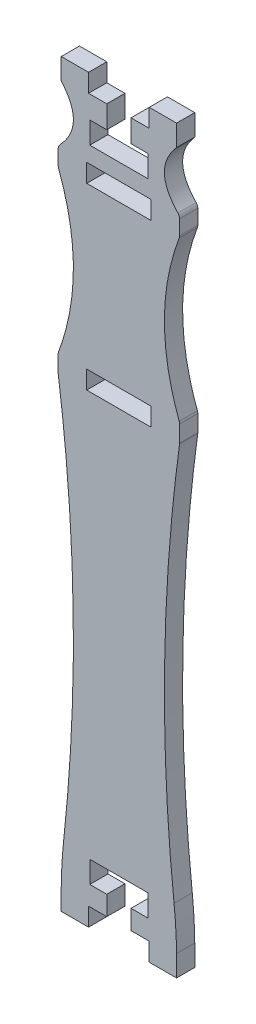
SolidWorks part; units mm, degrees
ref_plane "Alzado" through (0, 0, 0) normal (0, 0, 1) x (1, 0, 0)
ref_plane "Planta" through (0, 0, 0) normal (0, 1, 0) x (1, 0, 0)
ref_plane "Vista lateral" through (0, 0, 0) normal (1, 0, 0) x (0, 0, -1)
sketch "Croquis1" plane through (0, 0, 0) normal (0, 0, 1) x (1, 0, 0)
  line L1 (-10, 70) -> (-10, 67)
  line L2 (-7, 67) -> (-10, 67)
  line L4 (-15, 70) -> (-15, 67.4057)
  line L6 (-7, -45.5) -> (-7, -49)
  line L7 (-0.5, -42.5) -> (-9.5, -42.5)
  line L9 (-10, 70) -> (-15, 70)
  line L10 (-9.5, 60) -> (-0.5, 60)
  line L11 (-10, -52) -> (-10, -49)
  line L12 (-10, -52) -> (-15, -52)
  line L13 (-0.5, -42.5) -> (-0.5, -45.5)
  line L14 (-0.5, -45.5) -> (-3, -45.5)
  line L15 (-15, -52) -> (-15, -51.7014)
  line L16 (0, -49) -> (0, -52)
  line L17 (-0.5, 60) -> (-0.5, 63)
  line L18 (-3, -45.5) -> (-3, -49)
  line L19 (-0.5, 63) -> (-3, 63)
  line L20 (-10, 27.5) -> (-10, 24.5)
  line L21 (-3, 63) -> (-3, 67)
  line L22 (-10, 24.5) -> (0, 24.5)
  line L23 (0, 24.5) -> (0, 27.5)
  line L24 (-7, 63) -> (-7, 67)
  line L25 (-15, 27.3187) -> (-15, 24.5677)
  line L26 (-9.5, -45.5) -> (-7, -45.5)
  line L27 (-9.5, -42.5) -> (-9.5, -45.5)
  line L28 (-7, -49) -> (-10, -49)
  line L29 (-9.5, 63) -> (-7, 63)
  line L30 (-9.5, 60) -> (-9.5, 63)
  line L31 (-10, 54) -> (-10, 57)
  line L32 (-10, 54) -> (0, 54)
  line L33 (-10, 57) -> (0, 57)
  line L34 (0, 57) -> (0, 54)
  line L35 (-3, 67) -> (0, 67)
  line L36 (0, -52) -> (5, -52)
  line L37 (0, 67) -> (0, 70)
  line L38 (5, 70) -> (0, 70)
  line L39 (5, -52) -> (5, -51.7014)
  line L40 (0, 27.5) -> (-10, 27.5)
  line L42 (-15, 56.5943) -> (-15, 54.1813)
  line L43 (0, -49) -> (-3, -49)
  line L46 (-15, -49.0677) -> (-15, -51.7014)
  line L51 (5, -51.7014) -> (5, -49.0677)
  line L53 (5, 24.5677) -> (5, 27.3187)
  line L55 (5, 54.1813) -> (5, 56.5943)
  line L57 (5, 67.4057) -> (5, 70)
  arc A4 (-14.9909, -48.9331) -> (-15, -49.0677) centre (-14, -49.0677) ccw
  arc A5 (5, -49.0677) -> (4.9909, -48.9331) centre (4, -49.0677) ccw
  arc A6 (-15, 24.5677) -> (-14.9909, 24.4331) centre (-14, 24.5677) ccw
  arc A7 (4.9909, 24.4331) -> (5, 24.5677) centre (4, 24.5677) ccw
  arc A8 (-14.9371, 27.6678) -> (-15, 27.3187) centre (-14, 27.3187) ccw
  arc A9 (5, 27.3187) -> (4.9371, 27.6678) centre (4, 27.3187) ccw
  arc A10 (-14.7272, 57.2807) -> (-15, 56.5943) centre (-14, 56.5943) ccw
  arc A11 (-15, 54.1813) -> (-14.9371, 53.8322) centre (-14, 54.1813) ccw
  arc A12 (4.9371, 53.8322) -> (5, 54.1813) centre (4, 54.1813) ccw
  arc A13 (5, 56.5943) -> (4.7272, 57.2807) centre (4, 56.5943) ccw
  arc A14 (4.7272, 66.7193) -> (5, 67.4057) centre (4, 67.4057) ccw
  arc A15 (-15, 67.4057) -> (-14.7272, 66.7193) centre (-14, 67.4057) ccw
  spline S0 degree 3 poles (4.7272, 66.7193) (3.2424, 65.1462) (1.7576, 62) (3.2424, 58.8538) (4.7272, 57.2807) knots 0.028065 0.028065 0.028065 0.028065 0.5 0.971935 0.971935 0.971935 0.971935
  spline S1 degree 3 poles (-14.7272, 57.2807) (-13.2424, 58.8538) (-11.7576, 62) (-13.2424, 65.1462) (-14.7272, 66.7193) knots 0.028065 0.028065 0.028065 0.028065 0.5 0.971935 0.971935 0.971935 0.971935
  spline S2 degree 3 poles (-14.9371, 53.8322) (-13.3124, 49.4715) (-11.6876, 40.75) (-13.3124, 32.0285) (-14.9371, 27.6678) knots 0.006333 0.006333 0.006333 0.006333 0.5 0.993667 0.993667 0.993667 0.993667
  spline S3 degree 3 poles (4.9371, 53.8322) (3.3124, 49.4715) (1.6876, 40.75) (3.3124, 32.0285) (4.9371, 27.6678) knots 0.006333 0.006333 0.006333 0.006333 0.5 0.993667 0.993667 0.993667 0.993667
  spline S4 degree 3 poles (-14.9909, -48.9331) (-13.3303, -36.7054) (-11.6697, -12.25) (-13.3303, 12.2054) (-14.9909, 24.4331) knots 0.00091 0.00091 0.00091 0.00091 0.5 0.99909 0.99909 0.99909 0.99909
  spline S7 degree 3 poles (4.9909, -48.9331) (3.3303, -36.7054) (1.6697, -12.25) (3.3303, 12.2054) (4.9909, 24.4331) knots 0.00091 0.00091 0.00091 0.00091 0.5 0.99909 0.99909 0.99909 0.99909
extrude "Saliente-Extruir1" add sketch "Croquis1" along normal blind 3 contours L38 | L38 L37 L1 L9 L28 L6 L26 L27 L7 L13 L14 L18 L43 A6 A8 region at (-5, 8.2674, 0)
sketch "Croquis2" plane through (0, 0, 3) normal (0, 0, 1) x (1, 0, 0)
  line L0 (-3, 63) -> (-3, 67) construction
  line L1 (-9.5, 60) -> (-0.5, 60)
  line L3 (-9.5, 59.7) -> (-0.5, 59.7)
  line L5 (-0.5, 63) -> (-3, 63)
  line L7 (-0.5, 63.3) -> (-3, 63.3)
  line L8 (-3, 63) -> (-3, 63.3)
  line L9 (-3, -45.5) -> (-3, -49) construction
  line L10 (-7, 63) -> (-9.5, 63)
  line L11 (-7, 63) -> (-7, 63.3)
  line L12 (-7, 63.3) -> (-9.5, 63.3)
  line L15 (-9.5, 63) -> (-9.5, 60)
  line L17 (-9.8, 63) -> (-9.8, 60)
  line L19 (-0.5, 63) -> (-0.5, 60)
  line L21 (-0.2, 63) -> (-0.2, 60)
  line L22 (-0.5, -42.5) -> (-9.5, -42.5)
  line L23 (-0.5, -42.5) -> (-0.5, -42.2)
  line L24 (-0.5, -42.2) -> (-9.5, -42.2)
  line L27 (-0.5, -45.5) -> (-0.5, -42.5)
  line L28 (-0.5, -42.5) -> (-0.2, -42.5)
  line L29 (-0.2, -45.5) -> (-0.2, -42.5)
  line L31 (-9.5, -42.5) -> (-9.5, -45.5)
  line L33 (-9.8, -42.5) -> (-9.8, -45.5)
  line L34 (-0.5, -45.5) -> (-3, -45.5)
  line L36 (-0.5, -45.8) -> (-3, -45.8)
  line L37 (-3, -45.5) -> (-3, -45.8)
  line L38 (-7, -45.5) -> (-7, -49) construction
  line L39 (-9.5, -45.5) -> (-7, -45.5)
  line L41 (-9.5, -45.8) -> (-7, -45.8)
  line L42 (-7, -45.5) -> (-7, -45.8)
  line L43 (-9.8, -42.5) -> (-9.8, -42.2)
  line L44 (-9.8, -42.2) -> (-9.5, -42.2)
  line L45 (-9.8, -45.5) -> (-9.8, -45.8)
  line L46 (-9.8, -45.8) -> (-9.5, -45.8)
  line L47 (-0.5, -45.8) -> (-0.2, -45.8)
  line L48 (-0.2, -45.8) -> (-0.2, -45.5)
  line L49 (-0.2, -42.5) -> (-0.2, -42.2)
  line L50 (-0.2, -42.2) -> (-0.5, -42.2)
  line L51 (-0.2, 60) -> (-0.2, 59.7)
  line L52 (-0.2, 59.7) -> (-0.5, 59.7)
  line L53 (-0.5, 63.3) -> (-0.2, 63.3)
  line L54 (-0.2, 63.3) -> (-0.2, 63)
  line L55 (-9.8, 60) -> (-9.8, 59.7)
  line L56 (-9.8, 59.7) -> (-9.5, 59.7)
  line L57 (-9.8, 63) -> (-9.8, 63.3)
  line L58 (-9.8, 63.3) -> (-9.5, 63.3)
  line L60 (0, 54) -> (0.3, 54)
  line L61 (0, 54) -> (0, 57)
  line L62 (0, 57) -> (0.3, 57)
  line L63 (0.3, 54) -> (0.3, 57)
  line L64 (-10, 54) -> (-10.3, 54)
  line L65 (-10, 54) -> (-10, 57)
  line L66 (-10, 57) -> (-10.3, 57)
  line L67 (-10.3, 54) -> (-10.3, 57)
  line L68 (0, 27.5) -> (0.3, 27.5)
  line L69 (0, 27.5) -> (0, 24.5)
  line L70 (0, 24.5) -> (0.3, 24.5)
  line L71 (0.3, 27.5) -> (0.3, 24.5)
  line L72 (-10, 27.5) -> (-10.3, 27.5)
  line L73 (-10, 27.5) -> (-10, 24.5)
  line L74 (-10, 24.5) -> (-10.3, 24.5)
  line L75 (-10.3, 27.5) -> (-10.3, 24.5)
extrude "Cortar-Extruir2" cut sketch "Croquis2" against normal blind 3 contours L45 L46 L41 L42 L39 L31 L22 L23 L24 L44 L43 L33 | L47 L48 L29 L28 L27 L34 L37 L36 | L49 L50 L23 L28 | L72 L75 L74 L73 | L71 L68 L69 L70 | L60 L63 L62 L61 | L67 L64 L65 L66 | L58 L57 L17 L55 L56 L3 L52 L51 L21 L54 L53 L7 L8 L5 L19 L1 L15 L10 L11 L12 region at (-5, 59.8975, 3) region at (-5, -42.4003, 3) region at (-0.35, -42.5433, 3) region at (-0.35, -42.35, 3) region at (0.15, 55.5, 3) region at (-10.15, 55.5, 3) region at (0.15, 26, 3) region at (-10.15, 26, 3)
sketch "Croquis3" plane through (-15, 0, 0) normal (-1, 0, 0) x (0, 0, 1)
  line L1 (0, -52) -> (3, -52)
  line L2 (0, -52) -> (0, -48.5)
  line L3 (0, -48.5) -> (3, -48.5)
  line L4 (3, -52) -> (3, -48.5)
extrude "Cortar-Extruir3" cut sketch "Croquis3" against normal blind 0.5
sketch "Croquis4" plane through (5, 0, 0) normal (1, 0, 0) x (0, 0, -1)
  line L1 (-3, -52) -> (0, -52)
  line L2 (-3, -52) -> (-3, -48.5)
  line L3 (-3, -48.5) -> (0, -48.5)
  line L4 (0, -52) -> (0, -48.5)
extrude "Cortar-Extruir4" cut sketch "Croquis4" against normal blind 0.5
sketch "Croquis5" plane through (-15, 0, 0) normal (-1, 0, 0) x (0, 0, 1)
  line L1 (0, 70) -> (3, 70)
  line L2 (0, 70) -> (0, 66.5)
  line L3 (0, 66.5) -> (3, 66.5)
  line L4 (3, 70) -> (3, 66.5)
extrude "Cortar-Extruir5" cut sketch "Croquis5" against normal blind 0.5
sketch "Croquis6" plane through (5, 0, 0) normal (1, 0, 0) x (0, 0, -1)
  line L1 (0, 70) -> (-3, 70)
  line L2 (0, 70) -> (0, 66.5)
  line L3 (0, 66.5) -> (-3, 66.5)
  line L4 (-3, 70) -> (-3, 66.5)
extrude "Cortar-Extruir6" cut sketch "Croquis6" against normal blind 0.5
fillet "Redondeo1" radius 71 4 edges at (-14.9324, -48.5, 1.5) (4.9324, -48.5, 1.5) (4.525, 66.5, 1.5) (-14.525, 66.5, 1.5)
